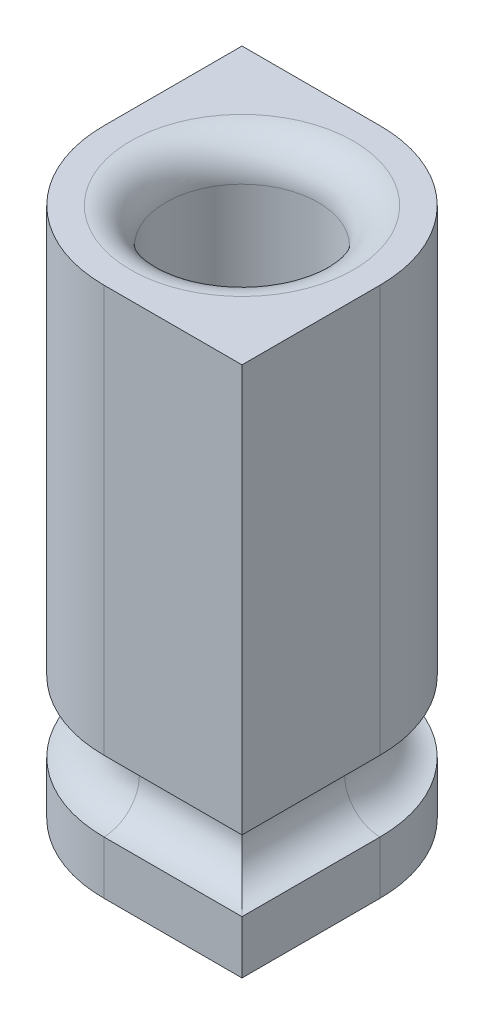
SolidWorks part; units mm, degrees
ref_plane "Front Plane" through (0, 0, 0) normal (0, 0, 1) x (1, 0, 0)
ref_plane "Top Plane" through (0, 0, 0) normal (0, 1, 0) x (1, 0, 0)
ref_plane "Right Plane" through (0, 0, 0) normal (1, 0, 0) x (0, 0, -1)
sketch "Sketch1" plane through (0, 0, 0) normal (0, 1, 0) x (1, 0, 0)
  line L1 (-3.9, 3.9) -> (0, 3.9)
  line L2 (-3.9, 3.9) -> (-3.9, 0)
  line L3 (0, -3.9) -> (3.9, -3.9)
  line L4 (3.9, 0) -> (3.9, -3.9)
  arc A0 (-3.9, 0) -> (0, -3.9) centre (0, 0) ccw
  arc A1 (3.9, 0) -> (0, 3.9) centre (0, 0) ccw
  point P0 (0, 0)
  dimension "D3" = 3.9
  dimension "D4" = 3.9
  dimension "D1" = 7.8
  dimension "D2" = 7.8
  dimension "D5" = 3.9
  dimension "D6" = 3.9
  dimension "D7" = 3.9
  dimension "D8" = 3.9
extrude "Boss-Extrude1" add sketch "Sketch1" along normal blind 5
ref_plane "Plane1" through (0, 2.5, 0) normal (0, 1, 0) x (1, 0, 0)
sketch "Sketch3" plane through (0, 2.5, 0) normal (0, 1, 0) x (1, 0, 0)
  line L0 (-3.9, 0) -> (-3.9, 3.9)
  line L1 (-3.9, 3.9) -> (0, 3.9)
  line L2 (3.9, 0) -> (3.9, -3.9)
  line L3 (3.9, -3.9) -> (0, -3.9)
  line L4 (-2.9, 0) -> (-2.9, 2.9)
  line L5 (-2.9, 2.9) -> (0, 2.9)
  line L6 (2.9, 0) -> (2.9, -2.9)
  line L7 (2.9, -2.9) -> (0, -2.9)
  arc A0 (-3.9, 0) -> (0, -3.9) centre (0, 0) ccw
  arc A1 (3.9, 0) -> (0, 3.9) centre (0, 0) ccw
  arc A2 (2.9, 0) -> (0, 2.9) centre (0, 0) ccw
  arc A3 (-2.9, 0) -> (0, -2.9) centre (0, 0) ccw
  dimension "D1" = 1
extrude "Cut-Extrude2" cut sketch "Sketch3" against normal blind 1 and the other way blind 1
fillet "Fillet1" radius 1 12 edges at (2.9, 3.5, 1.45) (2.0506, 3.5, -2.0506) (1.45, 3.5, 2.9) (-2.0506, 3.5, 2.0506) (2.9, 1.5, 1.45) (2.0506, 1.5, -2.0506) (-2.9, 1.5, -1.45) (1.45, 1.5, 2.9) (-1.45, 3.5, -2.9) (-2.9, 3.5, -1.45) (-1.45, 1.5, -2.9) (-2.0506, 1.5, 2.0506)
sketch "Sketch4" plane through (0, 5, 0) normal (0, 1, 0) x (1, 0, 0)
  line L0 (0, 3.9) -> (-3.9, 3.9)
  line L1 (-3.9, 3.9) -> (-3.9, 0)
  line L2 (3.9, 0) -> (3.9, -3.9)
  line L3 (3.9, -3.9) -> (0, -3.9)
  circle A0 centre (0, 0) radius 2.15
  arc A1 (3.9, 0) -> (0, 3.9) centre (0, 0) ccw
  arc A2 (-3.9, 0) -> (0, -3.9) centre (0, 0) ccw
  dimension "D1" = 4.3
extrude "Boss-Extrude3" add sketch "Sketch4" along normal blind 10
fillet "Fillet2" radius 1 1 edges at (0, 15, 2.15)
